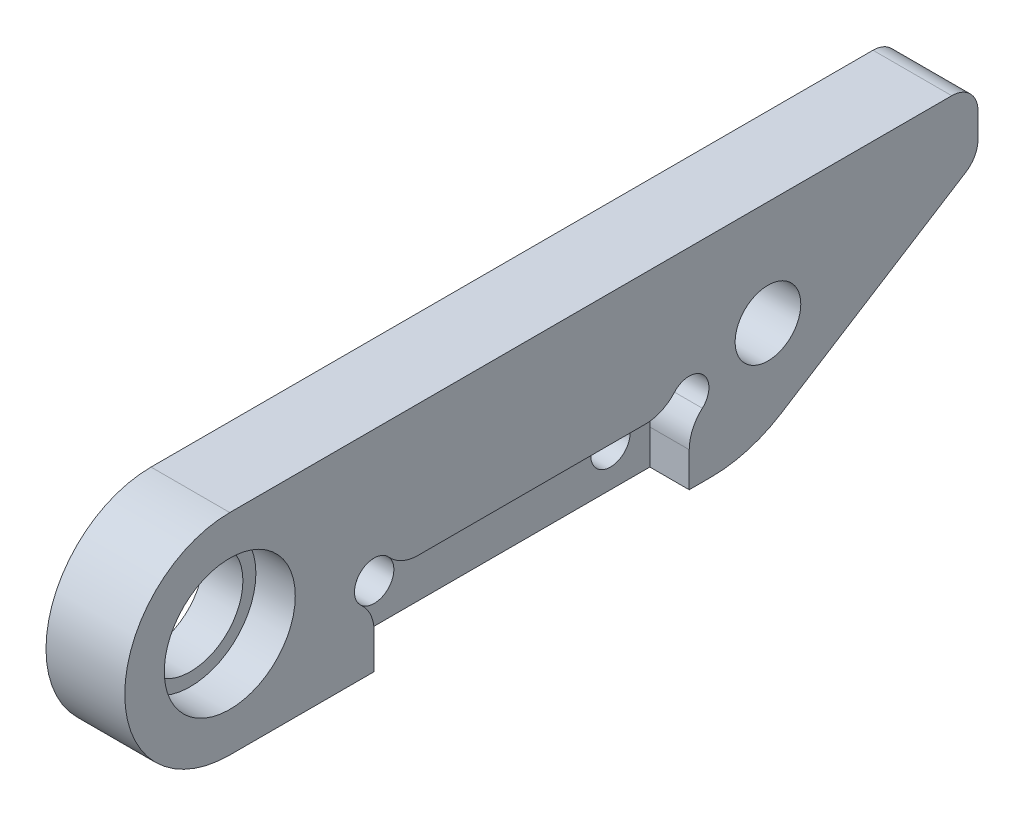
SolidWorks part; units mm, degrees
material "1060 Alloy"
ref_plane "Front Plane" through (0, 0, 0) normal (0, 0, 1) x (1, 0, 0)
ref_plane "Top Plane" through (0, 0, 0) normal (0, 1, 0) x (1, 0, 0)
ref_plane "Right Plane" through (0, 0, 0) normal (1, 0, 0) x (0, 0, -1)
sketch "Sketch27" plane through (0, 0, 0) normal (1, 0, 0) x (0, 0, -1)
  line L2 (9, 50) -> (66, 50)
  line L3 (9, 42) -> (30.9317, 42) construction
  line L4 (30.9317, 42) -> (30.9317, 54) construction
  line L6 (9, 34) -> (48.5644, 34)
  line L7 (30.9317, 54) -> (9, 42) construction
  line L8 (0, 0) -> (60, 0) construction
  line L9 (0, 0) -> (0, 58) construction
  line L10 (0, 58) -> (60, 58) construction
  line L11 (60, 0) -> (60, 58) construction
  line L12 (66, 50) -> (66, 45)
  line L13 (48.5644, 34) -> (66, 45)
  arc A0 (9, 50) -> (9, 34) centre (9, 42) ccw
  circle A1 centre (50, 42) radius 6 construction
  circle A3 centre (9, 42) radius 5.6 construction
  circle A5 centre (9, 42) radius 4
  circle A6 centre (50, 42) radius 2.5
  dimension "D9" = 12
  dimension "D10" = 5
  dimension "D12" = 8
  dimension "D13" = 8
  dimension "D14" = 5
  dimension "D6" = 16
  dimension "D16" = 11.2
  dimension "D1" = 60
  dimension "D2" = 58
  dimension "D3" = 42
  dimension "D4" = 9
  dimension "D5" = 50
  dimension "D7" = 42
  dimension "D8" = 12
  dimension "D17" = 25
extrude "Boss-Extrude1" add sketch "Sketch27" along normal blind 6
sketch "Sketch33" plane through (6, 0, 0) normal (1, 0, 0) x (0, 0, -1)
  circle A0 centre (9, 42) radius 4.99
  dimension "D1" = 9.98
extrude "Cut-Extrude2" cut sketch "Sketch33" against normal blind 3
sketch "Sketch34" plane through (6, 0, 0) normal (1, 0, 0) x (0, 0, -1)
  line L0 (20, 34) -> (44, 34)
  line L1 (20, 34) -> (20, 40)
  line L2 (44, 34) -> (44, 40)
  line L3 (20, 40) -> (44, 40)
  line L4 (9, 34) -> (48.5644, 34) construction
  circle A0 centre (50, 42) radius 2.5 construction
  dimension "D1" = 24
  dimension "D2" = 6
  dimension "D3" = 6
extrude "Cut-Extrude3" cut sketch "Sketch34" against normal blind 3
sketch "Sketch35" plane through (6, 0, 0) normal (1, 0, 0) x (0, 0, -1)
  circle A0 centre (20, 40) radius 1.5
  circle A1 centre (44, 40) radius 1.5
  dimension "D1" = 3
extrude "Cut-Extrude4" cut sketch "Sketch35" against normal up to surface (3 mm away) up to face at (3, 37, -32)
fillet "Fillet1" radius 3 4 edges at (4.5, 38.5, -44) (4.5, 40, -42.5) (4.5, 38.5, -20) (4.5, 40, -21.5)
sketch "Sketch36" plane through (3, 0, 0) normal (1, 0, 0) x (0, 0, -1)
  line L0 (20, 36.6459) -> (20, 34) construction
  line L1 (20, 34) -> (44, 34) construction
  line L2 (44, 34) -> (44, 36.6459) construction
  circle A0 centre (23, 37) radius 1.5
  circle A1 centre (41, 37) radius 1.5
  dimension "D1" = 3
  dimension "D2" = 3
  dimension "D3" = 3
  dimension "D4" = 3
  dimension "D5" = 3
extrude "Cut-Extrude5" cut sketch "Sketch36" against normal up to next
fillet "Fillet3" radius 2 2 edges at (3, 50, -66) (3, 45, -66)
fillet "Fillet4" radius 10 1 edges at (3, 34, -48.5644)
